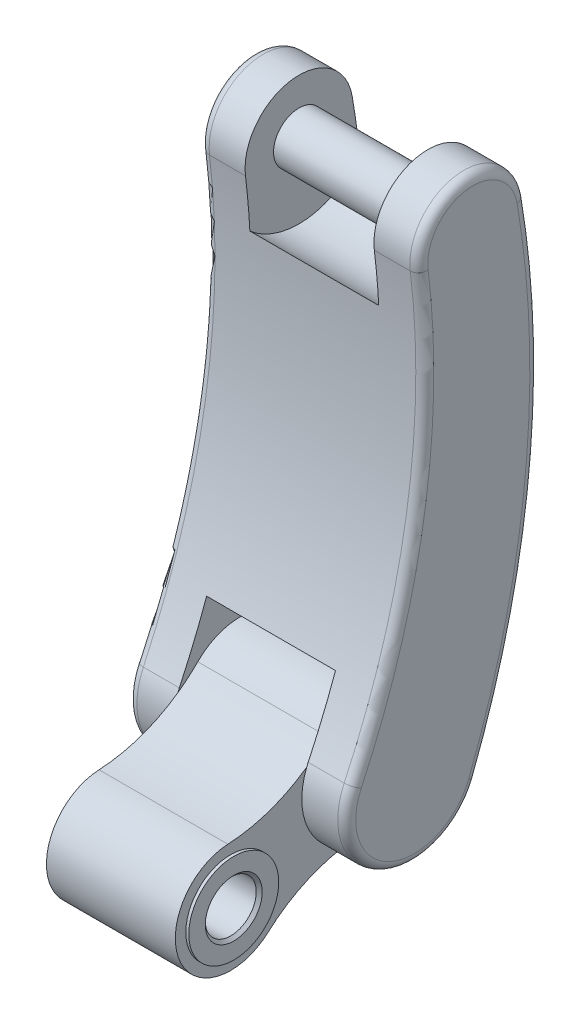
SolidWorks part; units mm, degrees
material "Balsa"
ref_plane "Front Plane" through (0, 0, 0) normal (0, 0, 1) x (1, 0, 0)
ref_plane "Top Plane" through (0, 0, 0) normal (0, 1, 0) x (1, 0, 0)
ref_plane "Right Plane" through (0, 0, 0) normal (1, 0, 0) x (0, 0, -1)
sketch "Sketch1" plane through (0, 0, 0) normal (1, 0, 0) x (0, 0, -1)
  line L0 (0, 0) -> (230.9699, 95.6709) construction
  line L1 (0, 0) -> (204.9591, 0) construction
  circle A0 centre (0, 0) radius 42.5
  arc A1 (-4.7599, 92.3775) -> (61.955, -68.6865) centre (0, 0) ccw
  arc A2 (230.5216, -4.3281) -> (159.9429, 166.0638) centre (230.9699, 95.6709) ccw
  arc A3 (159.9429, 166.0638) -> (-4.7599, 92.3775) centre (-17.6245, 342.0462) cw
  arc A4 (61.955, -68.6865) -> (230.5216, -4.3281) centre (229.4008, -254.3256) cw
  dimension "D1" = 85
  dimension "D2" = 185
  dimension "D5" = 200
  dimension "D6" = 250
  dimension "D7" = 250
  dimension "D3" = 22.5
  dimension "D4" = 250
extrude "Boss-Extrude1" add sketch "Sketch1" along normal mid plane 215
sketch "Sketch2" plane through (107.5, 0, 0) normal (1, 0, 0) x (0, 0, -1)
  circle A0 centre (0, 0) radius 42.5 construction
  circle A1 centre (0, 0) radius 42.5
  circle A2 centre (0, 0) radius 75
  dimension "D1" = 150
extrude "Boss-Extrude2" add sketch "Sketch2" along normal blind 5
sketch "Sketch3" plane through (-107.5, 0, 0) normal (-1, 0, 0) x (0, 0, 1)
  circle A0 centre (0, 0) radius 42.5 construction
  circle A1 centre (0, 0) radius 75
  circle A2 centre (0, 0) radius 75
  circle A3 centre (0, 0) radius 42.5
  dimension "D1" = 0
extrude "Boss-Extrude3" add sketch "Sketch3" along normal blind 5
chamfer "Chamfer1" distance 5 angle 45 2 edges at (-112.5, 0, 42.5) (112.5, 0, -42.5)
sketch "Sketch5" plane through (-107.5, 0, 0) normal (-1, 0, 0) x (0, 0, 1)
  line L0 (-230.9699, 95.6709) -> (-328.8645, 839.2545) construction
  line L1 (-230.9699, 95.6709) -> (293.1592, 95.6709) construction
  arc A0 (-159.9429, 166.0638) -> (-230.5216, -4.3281) centre (-230.9699, 95.6709) ccw construction
  arc A1 (-159.9429, 166.0638) -> (-230.5216, -4.3281) centre (-230.9699, 95.6709) ccw construction
  arc A2 (-335.7222, 54.6439) -> (-129.2246, 143.6724) centre (-230.9699, 95.6709) ccw
  arc A3 (-239.5266, 828.3583) -> (-417.5777, 854.4195) centre (-328.8645, 839.2545) ccw
  arc A4 (-239.5266, 828.3583) -> (-129.2246, 143.6724) centre (1001.2786, 677.0226) ccw
  arc A5 (-417.5777, 854.4195) -> (-335.7222, 54.6439) centre (1060.9749, 601.6699) ccw
  dimension "D1" = 225
  dimension "D4" = 180
  dimension "D5" = 1250
  dimension "D6" = 1500
  dimension "D2" = 750
  dimension "D3" = 97.5
extrude "Boss-Extrude4" add sketch "Sketch5" along normal blind 75
sketch "Sketch6" plane through (107.5, 0, 0) normal (1, 0, 0) x (0, 0, -1)
  arc A4 (129.2246, 143.6724) -> (239.5266, 828.3583) centre (-1001.2786, 677.0226) ccw
  arc A5 (417.5777, 854.4195) -> (239.5266, 828.3583) centre (328.8645, 839.2545) ccw
  arc A6 (335.7222, 54.6439) -> (417.5777, 854.4195) centre (-1060.9749, 601.6699) ccw
  arc A7 (129.2246, 143.6724) -> (335.7222, 54.6439) centre (230.9699, 95.6709) ccw
  arc A8 (129.2246, 143.6724) -> (239.5266, 828.3583) centre (-1001.2786, 677.0226) ccw
  arc A9 (417.5777, 854.4195) -> (239.5266, 828.3583) centre (328.8645, 839.2545) ccw
  arc A10 (335.7222, 54.6439) -> (417.5777, 854.4195) centre (-1060.9749, 601.6699) ccw
  arc A11 (129.2246, 143.6724) -> (335.7222, 54.6439) centre (230.9699, 95.6709) ccw
  dimension "D1" = 0
extrude "Boss-Extrude5" add sketch "Sketch6" along normal blind 75
fillet "Fillet2" radius 15 8 edges at (-182.5, -7.6368, -186.4303) (-182.5, 448.9455, -431.23) (-182.5, 928.3056, -315.8302) (-182.5, 478.2126, -232.8099) (182.5, 478.2126, -232.8099) (182.5, 928.3056, -315.8302) (182.5, 448.9455, -431.23) (182.5, -7.6368, -186.4303)
sketch "Sketch7" plane through (107.5, 0, 0) normal (-1, 0, 0) x (0, 0, 1)
  arc A0 (-239.5266, 828.3583) -> (-417.5777, 854.4195) centre (-328.8645, 839.2545) ccw construction
  arc A1 (-239.5266, 828.3583) -> (-417.5777, 854.4195) centre (-328.8645, 839.2545) ccw construction
  circle A2 centre (-328.8645, 839.2545) radius 42.5
  arc A3 (-417.5777, 854.4195) -> (-335.7222, 54.6439) centre (1060.9749, 601.6699) ccw construction
  arc A4 (-239.5266, 828.3583) -> (-129.2246, 143.6724) centre (1001.2786, 677.0226) ccw construction
  arc A5 (-430.0168, 765.8159) -> (-377.5663, 176.7001) centre (1060.9749, 601.6699) ccw
  arc A6 (-246.8772, 744.8984) -> (-174.7727, 253.4622) centre (1001.2786, 677.0226) ccw
  arc A7 (-430.0168, 765.8159) -> (-246.8772, 744.8984) centre (-328.8645, 839.2545) ccw
  arc A8 (-174.7727, 253.4622) -> (-377.5663, 176.7001) centre (-230.9699, 95.6709) ccw
  dimension "D1" = 85
  dimension "D2" = 250
  dimension "D3" = 335
extrude "Boss-Extrude6" add sketch "Sketch7" along normal up to surface (215 mm away) up to face at (-107.5, 283.5355, -257.3066)
